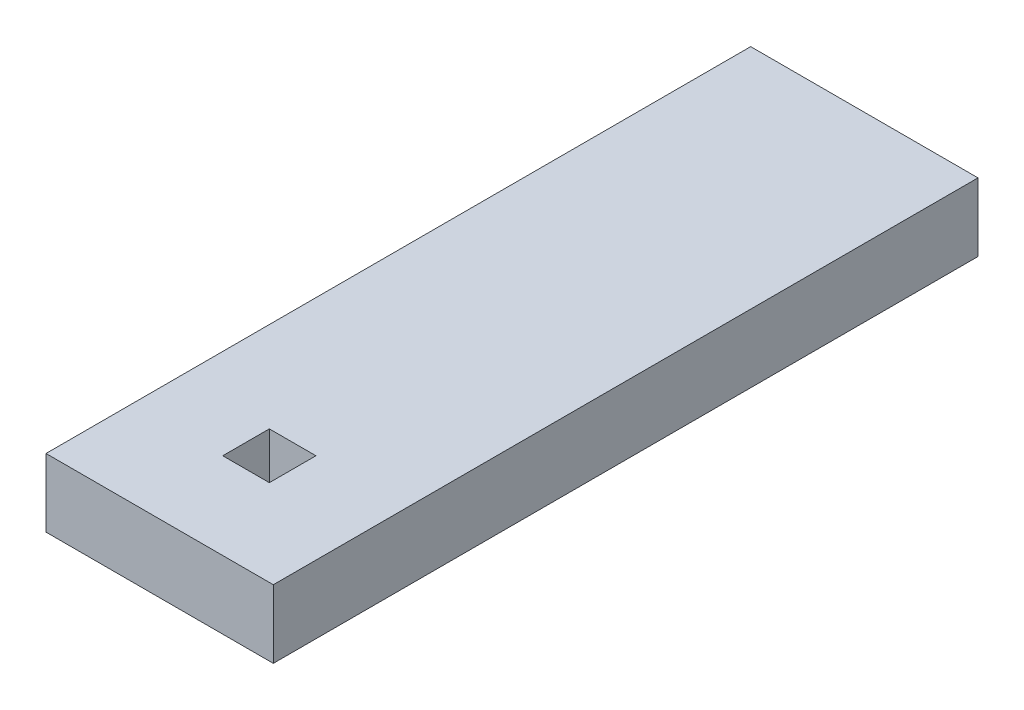
SolidWorks part; units mm, degrees
material "Acrylic (Medium-high impact)"
ref_plane "Front Plane" through (0, 0, 0) normal (0, 0, 1) x (1, 0, 0)
ref_plane "Top Plane" through (0, 0, 0) normal (0, 1, 0) x (1, 0, 0)
ref_plane "Right Plane" through (0, 0, 0) normal (1, 0, 0) x (0, 0, -1)
sketch "Sketch1" plane through (0, 0, 0) normal (0, 1, 0) x (1, 0, 0)
  line L0 (0, -10.675) -> (0, 0) construction
  line L1 (5, -15.5) -> (-5, -15.5)
  line L2 (5, -15.5) -> (5, 15.5)
  line L3 (5, 15.5) -> (-5, 15.5)
  line L4 (-5, -15.5) -> (-5, 15.5)
  line L5 (5, -15.5) -> (-5, 15.5) construction
  line L6 (5, 15.5) -> (-5, -15.5) construction
  line L7 (-1.025, -9.65) -> (1.025, -9.65)
  line L8 (-1.025, -9.65) -> (-1.025, -11.7)
  line L9 (-1.025, -11.7) -> (1.025, -11.7)
  line L10 (1.025, -9.65) -> (1.025, -11.7)
  line L11 (-1.025, -9.65) -> (1.025, -11.7) construction
  line L12 (-1.025, -11.7) -> (1.025, -9.65) construction
  point P0 (0, 0)
  point P6 (0, -10.675)
  dimension "D1" = 10
  dimension "D2" = 31
  dimension "D3" = 2.05
  dimension "D4" = 26.175
extrude "Boss-Extrude1" add sketch "Sketch1" along normal blind 2.9972 contours L1 L2 L3 L4 L7 L10 L9 L8 | L4 region at (0, 0, -0.1467)
equation "\"bottomThickness\"= .220in"
equation "\"wallThickness\"= .118in"
equation "\"D1@Boss-Extrude1\"=\"wallThickness\""
